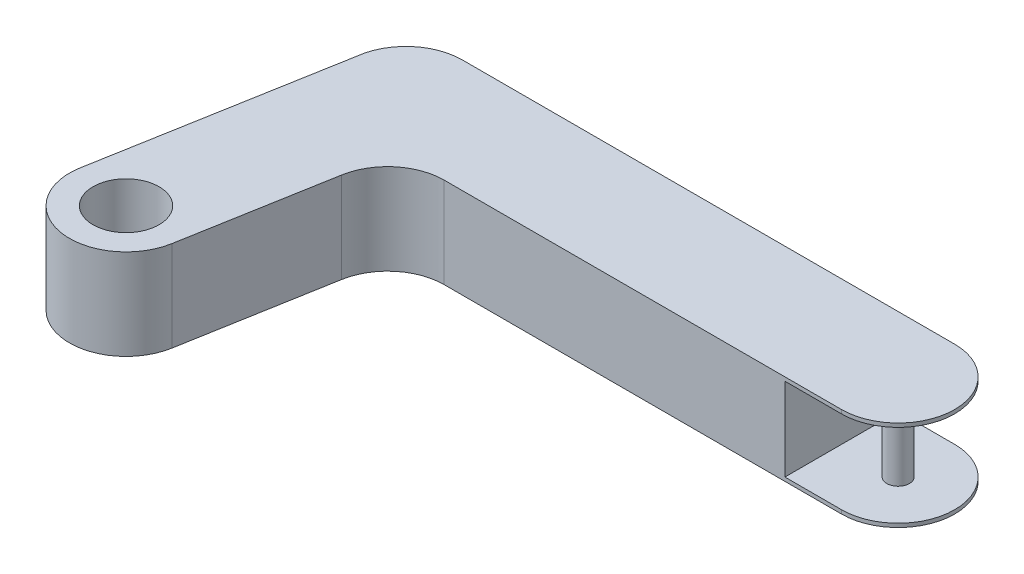
SolidWorks part; units mm, degrees
ref_plane "Front Plane" through (0, 0, 0) normal (0, 0, 1) x (1, 0, 0)
ref_plane "Top Plane" through (0, 0, 0) normal (0, 1, 0) x (1, 0, 0)
ref_plane "Right Plane" through (0, 0, 0) normal (1, 0, 0) x (0, 0, -1)
sketch "Sketch1" plane through (0, 0, 0) normal (0, 1, 0) x (1, 0, 0)
  line L0 (147.664, 0) -> (0, 0) construction
  line L1 (0, 0) -> (28.2356, 160.1322) construction
  line L2 (0, 0) -> (359.6628, 160.1322) construction
  line L3 (359.6628, 160.1322) -> (28.2356, 160.1322) construction
  line L4 (359.6628, 198.2322) -> (28.2356, 198.2322)
  line L5 (359.6628, 122.0322) -> (92.175, 122.0322)
  line L6 (-37.5166, 6.6421) -> (-8.6581, 169.6434)
  line L7 (37.5212, -6.616) -> (54.6538, 90.5482)
  circle A0 centre (0, 0) radius 22.225
  circle A1 centre (359.6628, 160.1322) radius 7.62
  arc A2 (-37.5166, 6.6421) -> (37.5212, -6.616) centre (0, 0) ccw
  arc A3 (359.6628, 122.0322) -> (359.6628, 198.2322) centre (359.6628, 160.1322) ccw
  arc A5 (28.2356, 198.2322) -> (-8.6581, 169.6434) centre (28.2356, 160.1322) ccw
  arc A6 (92.175, 122.0322) -> (54.6538, 90.5482) centre (92.175, 83.9322) ccw
  dimension "D1" = 24
  dimension "D2" = 38.1
  dimension "D3" = 80
  dimension "D5" = 38.1
  dimension "D7" = 38.1
  dimension "D8" = 15.24
  dimension "D9" = 44.45
  dimension "D4" = 80
  dimension "D6" = 393.7
  dimension "D10" = 163.0013
extrude "Boss-Extrude1" add sketch "Sketch1" along normal blind 30.48 and the other way blind 30.48
sketch "Sketch4" plane through (0, 0, -198.2322) normal (0, 0, -1) x (-1, 0, 0)
  line L0 (-397.7628, 0) -> (-397.7628, 27.94)
  line L1 (-397.7628, 30.48) -> (-397.7628, -30.48) construction
  line L2 (-397.7628, 27.94) -> (-321.5628, 27.94)
  line L3 (-321.5628, 27.94) -> (-321.5628, -27.94)
  line L4 (-321.5628, -27.94) -> (-397.7628, -27.94)
  line L5 (-397.7628, -27.94) -> (-397.7628, 0)
extrude "Cut-Extrude2" cut sketch "Sketch4" against normal up to surface (76.2 mm away) up to face at (225.9189, 0, -122.0322)
sketch "Sketch5" plane through (0, 0, 0) normal (0, 1, 0) x (1, 0, 0)
  circle A0 centre (359.6628, 160.1322) radius 7.62
extrude "Boss-Extrude3" add sketch "Sketch5" along normal up to surface and the other way up to surface up to face at (0, 30.48, 22.225) other way up to face at (359.6628, -30.48, -152.5122)
ref_axis "Axis1" through (0, -30.48, 0) along (0, 1, 0)
ref_point "Point1"
ref_axis "Axis2" through (359.6628, 27.94, -160.1322) along (0, -1, 0)
